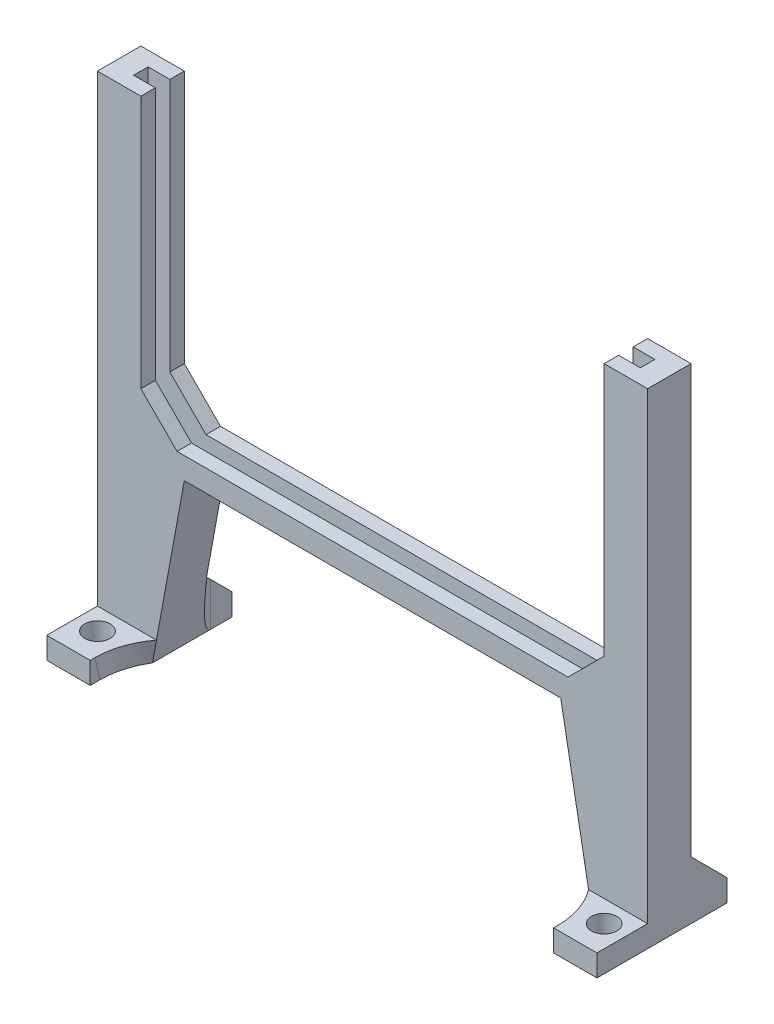
SolidWorks part; units mm, degrees
ref_plane "Front Plane" through (0, 0, 0) normal (0, 0, 1) x (1, 0, 0)
ref_plane "Top Plane" through (0, 0, 0) normal (0, 1, 0) x (1, 0, 0)
ref_plane "Right Plane" through (0, 0, 0) normal (1, 0, 0) x (0, 0, -1)
sketch "Sketch1" plane through (0, 0, 0) normal (0, 1, 0) x (1, 0, 0)
  line L1 (-3, 9) -> (3, 9)
  line L2 (-3, 9) -> (-3, -4)
  line L3 (-3, -4) -> (3, -4)
  line L4 (3, 9) -> (3, -4)
  line L5 (67, 9) -> (73, 9)
  line L6 (67, 9) -> (67, -4)
  line L7 (67, -4) -> (73, -4)
  line L8 (73, 9) -> (73, -4)
  circle A0 centre (0, 0) radius 1.75
  circle A1 centre (70, 0) radius 1.75
  point P13 (0, 9)
  point P14 (70, 9)
  point P15 (0, 0)
  point P16 (0, 0)
  point P17 (0, 0)
  dimension "D1" = 3.5
  dimension "D2" = 70
  dimension "D3" = 6
  dimension "D4" = 4
  dimension "D5" = 13
extrude "Boss-Extrude1" add sketch "Sketch1" along normal blind 3 contours L4 L1 L2 L3 A0 | L8 L5 L6 L7 A1 region at (0, 0, -2.8518) region at (70, 0, -2.8518)
ref_plane "Plane1" through (0, 0, -5) normal (0, 0, -1) x (-1, 0, 0)
sketch "Sketch3" plane through (0, 0, -5) normal (0, 0, -1) x (-1, 0, 0)
  line L0 (-73, 0) -> (-65.396, 0)
  line L1 (-67, 0) -> (-73, 0) construction
  line L2 (-65.396, 0) -> (-61, 24)
  line L3 (-61, 24) -> (-9, 24)
  line L4 (-9, 24) -> (-4.604, 0)
  line L5 (-4.604, 0) -> (3, 0)
  line L6 (-73, 0) -> (-73, 27)
  line L7 (-73, 27) -> (3, 27)
  line L8 (3, 27) -> (3, 0)
  dimension "D1" = 24
  dimension "D2" = 52
  dimension "D3" = 3
extrude "Boss-Extrude2" add sketch "Sketch3" against normal blind 2 and the other way up to surface (4 mm away) other way up to face at (0, 1.5, -9)
sketch "Sketch4" plane through (0, 27, 0) normal (0, 1, 0) x (1, 0, 0)
  line L0 (3, 9) -> (-3, 9)
  line L1 (-3, 9) -> (73, 9) construction
  line L2 (-3, 9) -> (-3, 3)
  line L3 (-3, 3) -> (3, 3)
  line L4 (-3, 3) -> (73, 3) construction
  line L5 (3, 3) -> (3, 5)
  line L6 (3, 5) -> (0, 5)
  line L7 (0, 5) -> (0, 7)
  line L8 (0, 7) -> (3, 7)
  line L9 (3, 7) -> (3, 9)
  line L10 (67, 3) -> (73, 3)
  line L11 (73, 3) -> (73, 9)
  line L12 (73, 9) -> (73, 3) construction
  line L13 (73, 9) -> (67, 9)
  line L14 (67, 9) -> (67, 7)
  line L15 (67, 7) -> (70, 7)
  line L16 (70, 7) -> (70, 5)
  line L17 (70, 5) -> (67, 5)
  line L18 (67, 5) -> (67, 3)
  dimension "D1" = 2
  dimension "D2" = 70
  dimension "D3" = 3
extrude "Boss-Extrude3" add sketch "Sketch4" along normal blind 40
sketch "Sketch5" plane through (0, 27, 0) normal (0, 1, 0) x (1, 0, 0)
  line L1 (0, 7) -> (70, 7)
  line L2 (0, 7) -> (0, 5)
  line L3 (0, 5) -> (70, 5)
  line L4 (70, 7) -> (70, 5)
extrude "Cut-Extrude1" cut sketch "Sketch5" against normal blind 2
chamfer "Chamfer1" distance 5 angle 45 4 edges at (67, 27, -4) (67, 27, -8) (3, 27, -8) (3, 27, -4)
fillet "Fillet1" radius 10 2 edges at (67, 1.5, -3) (3, 1.5, -3)
sketch "Sketch6" plane through (0, 0, -9) normal (0, 0, -1) x (-1, 0, 0)
  line L0 (-73, 3) -> (-64.8465, 3) construction
  line L1 (-73, 0) -> (-65.396, 0)
  line L2 (-73, 0) -> (-73, 3)
  line L3 (-73, 3) -> (-65.396, 3)
  line L4 (-65.396, 0) -> (-65.396, 3)
  line L6 (-4.604, 0) -> (3, 0)
  line L7 (-4.604, 0) -> (-4.604, 3)
  line L8 (-4.604, 3) -> (3, 3)
  line L9 (3, 0) -> (3, 3)
  line M9 (-4.604, 0) -> (3, 0)
  line M10 (3, 0) -> (3, 67)
extrude "Boss-Extrude4" add sketch "Sketch6" along normal blind 5 contours L8 L7 M9 M10 | L3 L4 L1 L2 region at (0.802, 1.5, -9)
fillet "Fillet2" radius 2 2 edges at (4.604, 1.5, -9) (65.396, 1.5, -9)
chamfer "Chamfer2" distance 5 angle 45 2 edges at (1.0768, 3, -9) (68.9232, 3, -9)
